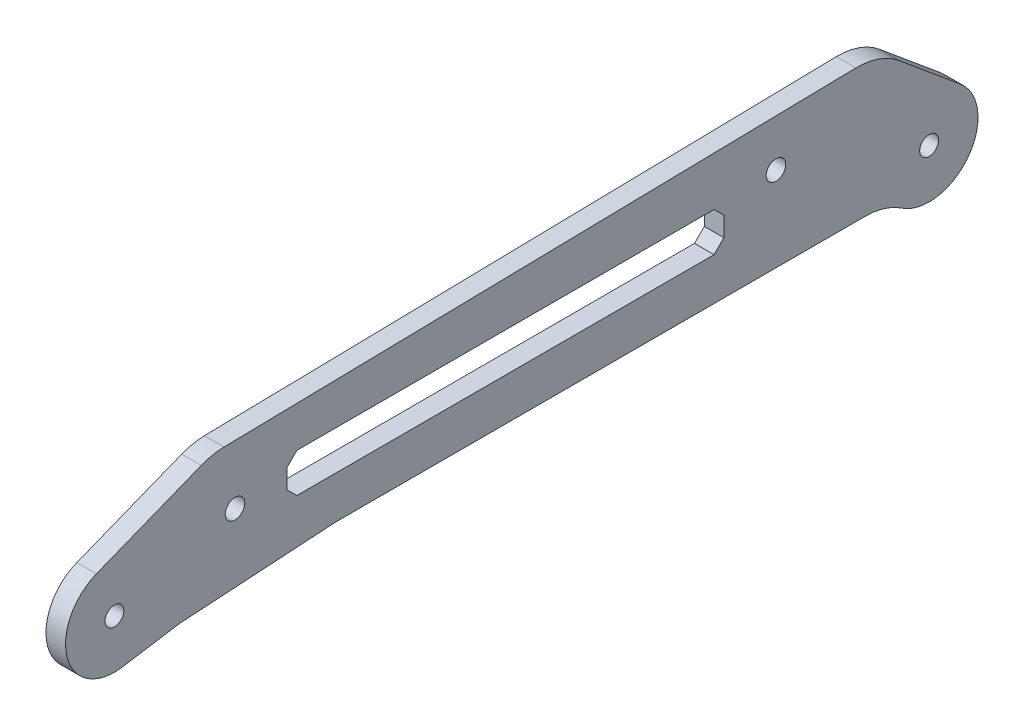
SolidWorks part; units mm, degrees
ref_plane "Front Plane" through (0, 0, 0) normal (0, 0, 1) x (1, 0, 0)
ref_plane "Top Plane" through (0, 0, 0) normal (0, 1, 0) x (1, 0, 0)
ref_plane "Right Plane" through (0, 0, 0) normal (1, 0, 0) x (0, 0, -1)
sketch "Sketch1" plane through (0, 0, 0) normal (1, 0, 0) x (0, 0, -1)
  line L0 (0, 0) -> (-125, 0) construction
  line L1 (-115, -6) -> (-91, -4.5)
  line L2 (-110, 14) -> (-7.5, 16)
  line L3 (-7.5, 16) -> (4.7978, 5.7646)
  line L4 (-98.5, 6.5) -> (-97, 8)
  line L5 (-127.7591, 6.974) -> (-110, 14)
  line L6 (-115, -6) -> (-123.8188, -7.4064)
  line L7 (-91, -4.5) -> (-6, -4.5)
  line L8 (-58.75, 15) -> (-65, 5.6263) construction
  line L9 (-97, 8) -> (-33, 8)
  line L10 (-98.5, 6.5) -> (-98.5, 3.5)
  line L11 (-97, 2) -> (-33, 2)
  line L12 (-31.5, 6.5) -> (-31.5, 3.5)
  line L13 (-98.5, 3.5) -> (-97, 2)
  line L14 (-33, 8) -> (-31.5, 6.5)
  line L15 (-33, 2) -> (-31.5, 3.5)
  circle A0 centre (0, 0) radius 7.5
  circle A1 centre (-125, 0) radius 7.5
  circle A2 centre (-23.5, 8.5) radius 1.5
  circle A3 centre (0, 0) radius 1.45
  circle A4 centre (-125, 0) radius 1.45
  circle A8 centre (-106.5, 5) radius 1.5
  point P16 (-98.5, 8)
  point P17 (-31.5, 2)
  point P18 (-98.5, 2)
  point P22 (-31.5, 8)
  dimension "D1" = 15
  dimension "D3" = 15
  dimension "D4" = 6.25
  dimension "D5" = 2.9
  dimension "D7" = 15
  dimension "D9" = 23.5
  dimension "D10" = 7.5
  dimension "D6" = 10
  dimension "D13" = 6
  dimension "D14" = 4.5
  dimension "D18" = 8
  dimension "D19" = 3
  dimension "D20" = 5
  dimension "D21" = 18.5
  dimension "D12" = 8.5
  dimension "D2" = 125
  dimension "D8" = 14
  dimension "D11" = 16
  dimension "D15" = 85
  dimension "D16" = 6.5
  dimension "D17" = 6
  dimension "D22" = 8
extrude "Boss-Extrude1" add sketch "Sketch1" along normal mid plane 3 contours A3 A0 | A1 A4 | L0 A0 L2 L5 A1 | A0 L0 A1 L6 L1 L7 region at (0, -5.3739, 119.6214) region at (0, -1.9259, 132.0288) region at (0, 5.2821, 5.0212)
fillet "Fillet1" radius 10 5 edges at (0, -4.5, 91) (0, -6, 115) (0, -4.5, 6) (0, 14, 110) (0, 16, 7.5)
